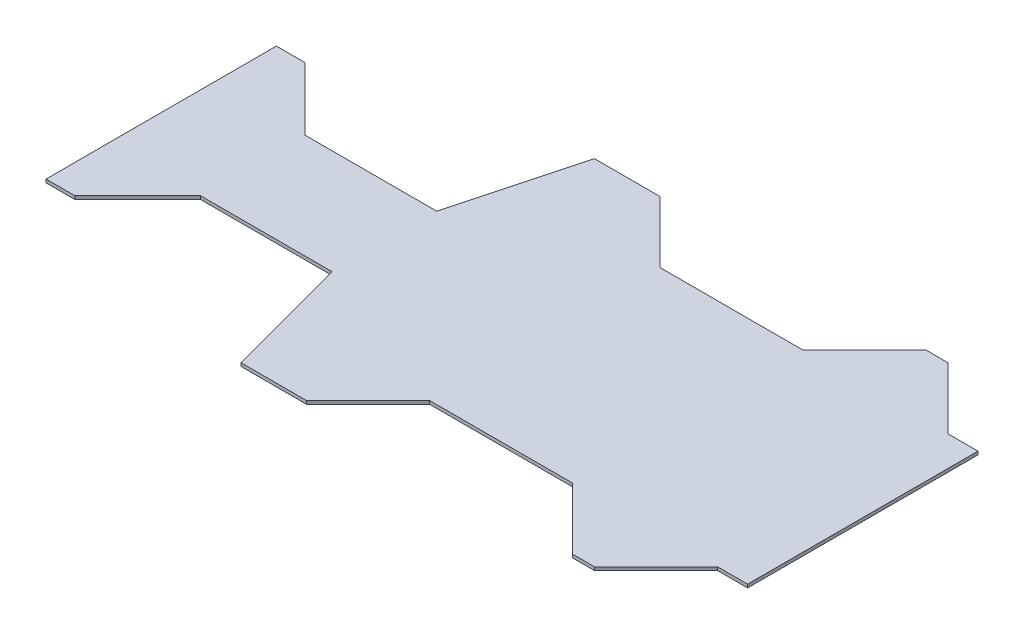
SolidWorks part; units mm, degrees
ref_plane "Front Plane" through (0, 0, 0) normal (0, 0, 1) x (1, 0, 0)
ref_plane "Top Plane" through (0, 0, 0) normal (0, 1, 0) x (1, 0, 0)
ref_plane "Right Plane" through (0, 0, 0) normal (1, 0, 0) x (0, 0, -1)
other "avc2012"
sketch "Sketch1" plane through (0, 0, 0) normal (0, 1, 0) x (1, 0, 0)
  line L0 (125.73, -85.725) -> (115.1774, -85.725)
  line L1 (-170.18, 0) -> (170.18, 0) construction
  line L2 (-170.18, -55.88) -> (-170.18, 55.88)
  line L3 (-170.18, -55.88) -> (-156.21, -55.88)
  line L4 (170.18, -55.88) -> (170.18, 55.88)
  line L5 (115.1774, -85.725) -> (85.3324, -55.88)
  line L6 (85.3324, -55.88) -> (15.875, -55.88)
  line L7 (15.875, -55.88) -> (-13.97, -85.725)
  line L8 (125.73, -85.725) -> (155.575, -55.88)
  line L9 (-45.72, 85.725) -> (-61.884, 25.4)
  line L10 (-156.21, -55.88) -> (-125.73, -25.4)
  line L11 (-125.73, -25.4) -> (-61.884, -25.4)
  line L12 (-13.97, -85.725) -> (-45.72, -85.725)
  line L13 (155.575, -55.88) -> (170.18, -55.88)
  line L14 (-45.72, -85.725) -> (-61.884, -25.4)
  line L15 (155.575, 55.88) -> (170.18, 55.88)
  line L16 (-13.97, 85.725) -> (-45.72, 85.725)
  line L17 (-125.73, 25.4) -> (-61.884, 25.4)
  line L18 (-156.21, 55.88) -> (-125.73, 25.4)
  line L19 (125.73, 85.725) -> (155.575, 55.88)
  line L20 (15.875, 55.88) -> (-13.97, 85.725)
  line L21 (85.3324, 55.88) -> (15.875, 55.88)
  line L22 (115.1774, 85.725) -> (85.3324, 55.88)
  line L23 (-170.18, 55.88) -> (-156.21, 55.88)
  line L24 (125.73, 85.725) -> (115.1774, 85.725)
  dimension "D1" = 340.36
  dimension "D2" = 111.76
  dimension "D3" = 31.75
  dimension "D4" = 50.8
  dimension "D5" = 85.725
  dimension "D6" = 135
  dimension "D7" = 171.45
  dimension "D8" = 135
  dimension "D9" = 135
  dimension "D10" = 105
  dimension "D11" = 44.45
  dimension "D12" = 44.45
extrude "Plate" add sketch "Sketch1" along normal blind 1.5875
ref_plane "Yplane" through (-170.18, 0, 0) normal (-1, 0, 0) x (0, 0, 1)
ref_plane "Xplane" through (0, 0, 85.725) normal (0, 0, 1) x (1, 0, 0)
